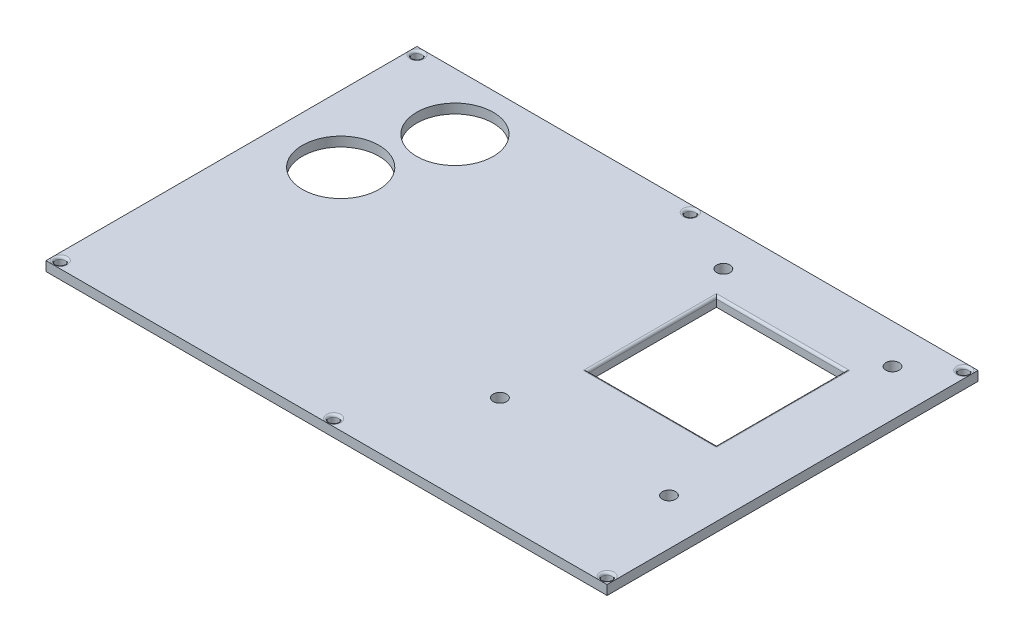
SolidWorks part; units mm, degrees
ref_plane "Front Plane" through (0, 0, 0) normal (0, 0, 1) x (1, 0, 0)
ref_plane "Top Plane" through (0, 0, 0) normal (0, 1, 0) x (1, 0, 0)
ref_plane "Right Plane" through (0, 0, 0) normal (1, 0, 0) x (0, 0, -1)
sketch "Sketch1" plane through (0, 0, 0) normal (0, 1, 0) x (1, 0, 0)
  line L1 (-59, 39) -> (59, 39)
  line L2 (-59, 39) -> (-59, -39)
  line L3 (-59, -39) -> (59, -39)
  line L4 (59, 39) -> (59, -39)
  line L5 (-59, 39) -> (59, -39) construction
  line L6 (-59, -39) -> (59, 39) construction
  point P0 (0, 0)
  dimension "D1" = 118
  dimension "D2" = 78
extrude "Boss-Extrude1" add sketch "Sketch1" along normal blind 2
sketch "Sketch2" plane through (0, 2, 0) normal (0, 1, 0) x (1, 0, 0)
  line L0 (-59, -39) -> (59, -39) construction
  line L1 (-59, 39) -> (-24, 39) construction
  line L2 (-59, 39) -> (-59, -39) construction
  line L3 (-59, -39) -> (-24, -39) construction
  line L5 (-39, 27) -> (-39, 2.5468) construction
  line L6 (-59, 39) -> (-39, 39) construction
  line L7 (-59, 39) -> (-59, 27) construction
  line L8 (-59, 27) -> (-39, 27) construction
  line L9 (-39, 39) -> (-39, 27) construction
  circle A0 centre (-39, 27) radius 8.05
  circle A1 centre (-45, 8.9722) radius 8.05
  circle A2 centre (-39, 27) radius 9.5 construction
  circle A3 centre (-45, 8.9722) radius 9.5 construction
  point P7 (0, 0)
  point P17 (0, 0)
  point P18 (0, 0)
  point P19 (0, 0)
  point P20 (-39, 2.682)
  dimension "D2" = 16.1
  dimension "D3" = 19
  dimension "D4" = 12
  dimension "D5" = 14
  dimension "D1" = 20
extrude "Buttons" cut sketch "Sketch2" against normal blind 2
sketch "Sketch3" plane through (0, 2, 0) normal (0, 1, 0) x (1, 0, 0)
  line L0 (59, -39) -> (59, 39) construction
  line L1 (18, 25) -> (45, 25)
  line L2 (18, 25) -> (18, -2)
  line L3 (18, -2) -> (45, -2)
  line L4 (45, 25) -> (45, -2)
  line L9 (59, 39) -> (-59, 39) construction
  line L14 (31.5, 25) -> (31.5, 36.1162) construction
  line L15 (13.72, 30.7313) -> (49.28, 30.7313) construction
  line L16 (13.72, 30.7313) -> (13.72, -16.2587) construction
  line L17 (13.72, -16.2587) -> (49.28, -16.2587) construction
  line L18 (49.28, 30.7313) -> (49.28, -16.2587) construction
  circle A0 centre (13.72, 30.7313) radius 1.4
  circle A1 centre (49.28, 30.7313) radius 1.4
  circle A2 centre (13.72, -16.2587) radius 1.4
  circle A3 centre (49.28, -16.2587) radius 1.4
  point P22 (31.5, 30.7313)
  dimension "D3" = 2.8
  dimension "D1" = 27
  dimension "D2" = 27
  dimension "D8" = 14
  dimension "D9" = 14
  dimension "D10" = 35.56
  dimension "D11" = 46.99
extrude "OLED" cut sketch "Sketch3" against normal blind 2
sketch "Sketch4" plane through (0, 2, 0) normal (0, 1, 0) x (1, 0, 0)
  line L0 (59, 39) -> (-59, 39) construction
  line L1 (-57.5, 37.5) -> (57.5, 37.5) construction
  line L2 (-57.5, 37.5) -> (-57.5, -37.5) construction
  line L3 (-57.5, -37.5) -> (57.5, -37.5) construction
  line L4 (57.5, 37.5) -> (57.5, -37.5) construction
  line L5 (59, -39) -> (59, 39) construction
  line L6 (-59, -39) -> (59, -39) construction
  line L7 (-59, 39) -> (-59, -39) construction
  circle A0 centre (-57.5, 37.5) radius 1
  circle A1 centre (-57.5, -37.5) radius 1
  circle A2 centre (57.5, -37.5) radius 1
  circle A3 centre (57.5, 37.5) radius 1
  circle A4 centre (0, 37.5) radius 1
  circle A5 centre (0, -37.5) radius 1
  dimension "D5" = 2
  dimension "D1" = 1.5
  dimension "D2" = 1.5
  dimension "D3" = 1.5
  dimension "D4" = 1.5
extrude "Screw Holes" cut sketch "Sketch4" against normal blind 2
fillet "Fillets" radius 0.5 10 edges at (18, 2, -11.5) (31.5, 2, -25) (45, 2, -11.5) (31.5, 2, 2) (57.5, 2, 38.5) (57.5, 2, -36.5) (0, 2, -36.5) (0, 2, 38.5) (-57.5, 2, 38.5) (-57.5, 2, -36.5)
